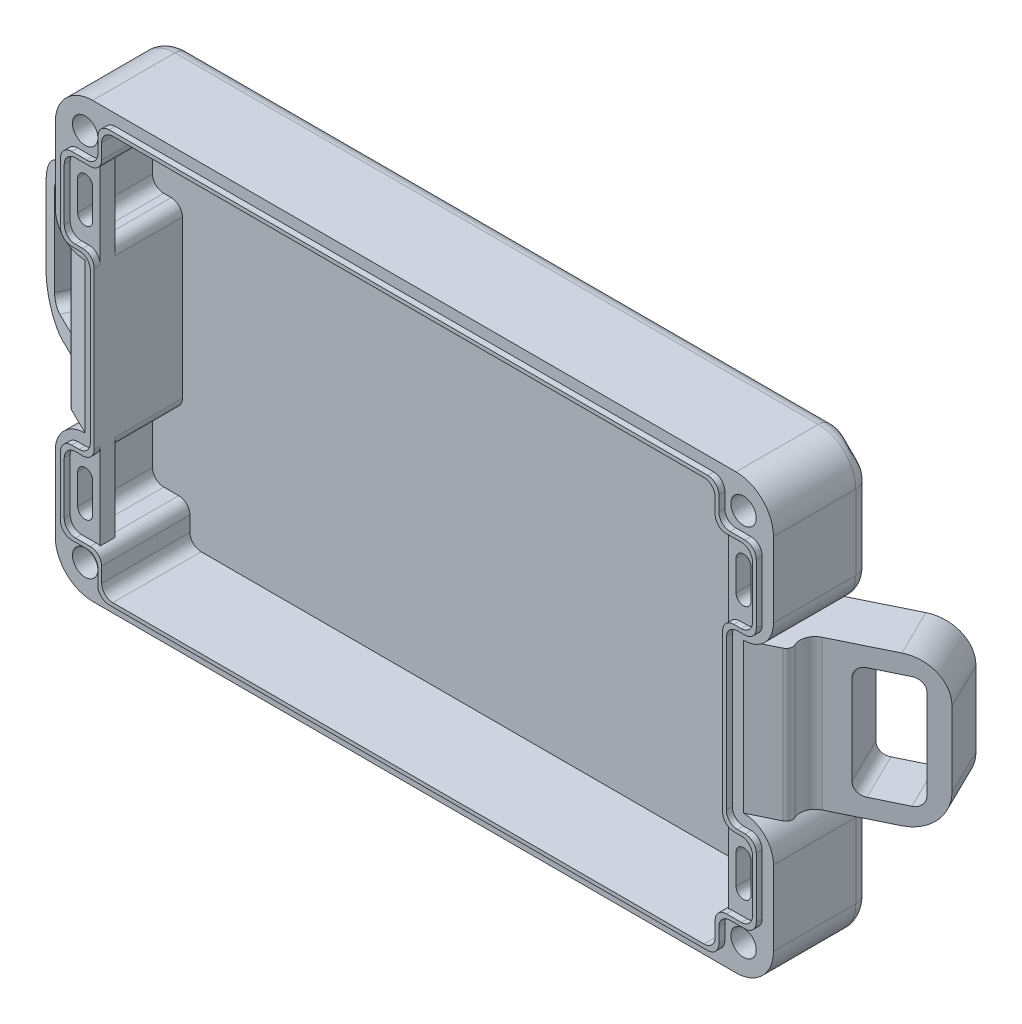
SolidWorks part; units mm, degrees
ref_plane "Спереди" through (0, 0, 0) normal (0, 0, 1) x (1, 0, 0)
ref_plane "Сверху" through (0, 0, 0) normal (0, 1, 0) x (1, 0, 0)
ref_plane "Справа" through (0, 0, 0) normal (1, 0, 0) x (0, 0, -1)
sketch "Sketch1" plane through (0, 0, 0) normal (0, 0, 1) x (1, 0, 0)
  line L1 (-48, 58) -> (48, 58) construction
  line L2 (-48, 58) -> (-48, 0) construction
  line L3 (-48, 0) -> (48, 0) construction
  line L5 (-48, 29) -> (32, 29) construction
  line L7 (0, 0) -> (0, 58) construction
  line L10 (-48, 58) -> (-48, 0) construction
  line L11 (-48, 58) -> (48, 58)
  line L12 (48, 58) -> (48, 0) construction
  line L13 (48, 0) -> (-48, 0)
  line L14 (48, 19) -> (44, 19)
  line L15 (44, 19) -> (44, 39)
  line L16 (44, 39) -> (48, 39)
  line L17 (-44, 39) -> (-48, 39)
  line L18 (-44, 19) -> (-44, 39)
  line L19 (-48, 19) -> (-44, 19)
  line L20 (48, 0) -> (48, 19)
  line L21 (48, 39) -> (48, 58)
  line L22 (-48, 0) -> (-48, 19)
  line L23 (-48, 39) -> (-48, 58)
  dimension "D1" = 96
  dimension "D2" = 58
  dimension "D3" = 4
  dimension "D4" = 10
  dimension "D5" = 10
extrude "Boss-Extrude1" add sketch "Sketch1" along normal blind 13
shell "Shell1" thickness 2 removed face at (0, 29, 13)
sketch "Sketch3" plane through (0, 0, 2) normal (0, 0, 1) x (1, 0, 0)
  line L0 (0, 0) -> (0, 58) construction
  line L1 (46, 2) -> (41, 2)
  line L2 (46, 2) -> (46, 7)
  line L3 (46, 7) -> (41, 7)
  line L4 (41, 2) -> (41, 7)
  line L5 (-48, 0) -> (48, 0) construction
  line L6 (48, 58) -> (-48, 58) construction
  line L7 (-41, 2) -> (-41, 7)
  line L9 (44, 29) -> (-44, 29) construction
  line L11 (-46, 7) -> (-41, 7)
  line L12 (-46, 2) -> (-46, 7)
  line L13 (-46, 2) -> (-41, 2)
  line L14 (-46, 56) -> (-41, 56)
  line L15 (-46, 56) -> (-46, 51)
  line L16 (-46, 51) -> (-41, 51)
  line L17 (-41, 56) -> (-41, 51)
  line L18 (41, 56) -> (41, 51)
  line L19 (46, 51) -> (41, 51)
  line L20 (46, 56) -> (46, 51)
  line L21 (46, 56) -> (41, 56)
  line L22 (48, 0) -> (48, 19) construction
  line L23 (44, 19) -> (44, 39) construction
  line L24 (-44, 39) -> (-44, 19) construction
  circle A0 centre (44, 4) radius 1.7
  circle A1 centre (-44, 4) radius 1.7
  circle A2 centre (-44, 54) radius 1.7
  circle A3 centre (44, 54) radius 1.7
  dimension "D3" = 3.4
  dimension "D1" = 5
  dimension "D2" = 5
  dimension "D4" = 4
  dimension "D5" = 4
extrude "Boss-Extrude3" add sketch "Sketch3" along normal up to surface (11 mm away) up to face at (0, 29, 13)
sketch "Sketch2" plane through (0, 0, 2) normal (0, 0, 1) x (1, 0, 0)
  line L0 (0, 0) -> (0, 58) construction
  line L5 (-48, 0) -> (48, 0) construction
  line L6 (48, 58) -> (-48, 58) construction
  line L7 (44, 19) -> (44, 39) construction
  line L9 (-44, 29) -> (44, 29) construction
  line L11 (-44, 39) -> (-44, 19) construction
  circle A0 centre (-29, 44.5) radius 2.5
  circle A1 centre (29, 44.5) radius 2.5
  circle A2 centre (29, 13.5) radius 2.5
  circle A3 centre (-29, 13.5) radius 2.5
  circle A4 centre (-29, 44.5) radius 1.25
  circle A5 centre (29, 44.5) radius 1.25
  circle A6 centre (29, 13.5) radius 1.25
  circle A7 centre (-29, 13.5) radius 1.25
  dimension "D3" = 5
  dimension "D4" = 29
  dimension "D8" = 31
  dimension "D9" = 2.5
  dimension "D1" = 2
  dimension "D2" = 2
sketch "Sketch5" plane through (0, 0, 13) normal (0, 0, 1) x (1, 0, 0)
  line L0 (0, 0) -> (0, 58) construction
  line L1 (-48, 0) -> (48, 0) construction
  line L2 (48, 58) -> (-48, 58) construction
  line L4 (46, 7) -> (46, 17) construction
  line L5 (44, 29) -> (-42, 29) construction
  line L6 (46, 7) -> (46, 17) construction
  line L8 (46, 7) -> (41, 7)
  line L9 (41, 7) -> (41, 2)
  line L10 (41, 2) -> (0, 2)
  line L11 (-41, 2) -> (41, 2) construction
  line L38 (44, 19) -> (44, 39) construction
  line L39 (-42, 41) -> (-42, 17) construction
  line L40 (42.5, 17.5) -> (42.5, 29)
  line L41 (46.5, 17.5) -> (42.5, 17.5)
  line L42 (46, 7) -> (46, 17)
  line L43 (46, 17) -> (42, 17) construction
  line L44 (46, 17) -> (42, 17) construction
  line L45 (46, 17) -> (42, 17)
  line L46 (42, 17) -> (42, 29)
  line L47 (42, 17) -> (42, 41) construction
  line L48 (46.5, 6.5) -> (46.5, 17.5)
  line L49 (46.5, 6.5) -> (41.5, 6.5)
  line L50 (41.5, 6.5) -> (41.5, 1.5)
  line L51 (41.5, 1.5) -> (0, 1.5)
  line L52 (-41.5, 1.5) -> (0, 1.5)
  line L53 (-41.5, 6.5) -> (-41.5, 1.5)
  line L54 (-46.5, 6.5) -> (-41.5, 6.5)
  line L55 (-46.5, 6.5) -> (-46.5, 17.5)
  line L56 (-42, 17) -> (-42, 41)
  line L57 (-46, 17) -> (-42, 17)
  line L58 (-46, 7) -> (-46, 17)
  line L59 (-46.5, 17.5) -> (-42.5, 17.5)
  line L60 (-42.5, 17.5) -> (-42.5, 40.5)
  line L61 (-41, 2) -> (0, 2)
  line L62 (-41, 7) -> (-41, 2)
  line L63 (-46, 7) -> (-41, 7)
  line L64 (-46, 51) -> (-41, 51)
  line L65 (-41, 51) -> (-41, 56)
  line L66 (-41, 56) -> (0, 56)
  line L67 (-46.5, 40.5) -> (-42.5, 40.5)
  line L68 (-46, 51) -> (-46, 41)
  line L69 (-46, 41) -> (-42, 41)
  line L70 (-46.5, 51.5) -> (-46.5, 40.5)
  line L71 (-46.5, 51.5) -> (-41.5, 51.5)
  line L72 (-41.5, 51.5) -> (-41.5, 56.5)
  line L73 (-41.5, 56.5) -> (0, 56.5)
  line L74 (41.5, 56.5) -> (0, 56.5)
  line L75 (41.5, 51.5) -> (41.5, 56.5)
  line L76 (46.5, 51.5) -> (41.5, 51.5)
  line L77 (46.5, 51.5) -> (46.5, 40.5)
  line L78 (42, 41) -> (42, 29)
  line L79 (46, 41) -> (42, 41)
  line L80 (46, 51) -> (46, 41)
  line L81 (46.5, 40.5) -> (42.5, 40.5)
  line L82 (42.5, 40.5) -> (42.5, 29)
  line L83 (41, 56) -> (0, 56)
  line L84 (41, 51) -> (41, 56)
  line L85 (46, 51) -> (41, 51)
  point P58 (-42.5, 29)
  dimension "D1" = 0.5
extrude "Boss-Extrude4" add sketch "Sketch5" along normal blind 0.8
fillet "Fillet6" radius 1.5 20 edges at (-41, 2, 7.9) (-41, 7, 7.9) (-46, 7, 7.9) (-46, 17, 7.9) (-42, 17, 7.9) (-42, 41, 7.9) (-46, 41, 7.9) (-46, 51, 7.9) (-41, 51, 7.9) (-41, 56, 7.9) (41, 56, 7.9) (41, 51, 7.9) (46, 51, 7.9) (46, 41, 7.9) (42, 41, 7.9) (42, 17, 7.9) (46, 17, 7.9) (41, 2, 7.9) (46, 7, 7.9) (41, 7, 7.9)
fillet "Fillet7" radius 1.5 20 edges at (46.5, 6.5, 13.4) (41.5, 6.5, 13.4) (41.5, 1.5, 13.4) (-41.5, 1.5, 13.4) (-41.5, 6.5, 13.4) (-46.5, 6.5, 13.4) (-46.5, 17.5, 13.4) (-42.5, 17.5, 13.4) (-42.5, 40.5, 13.4) (-46.5, 40.5, 13.4) (-46.5, 51.5, 13.4) (-41.5, 51.5, 13.4) (-41.5, 56.5, 13.4) (41.5, 56.5, 13.4) (41.5, 51.5, 13.4) (46.5, 51.5, 13.4) (46.5, 40.5, 13.4) (42.5, 40.5, 13.4) (42.5, 17.5, 13.4) (46.5, 17.5, 13.4)
sketch "Sketch6" plane through (44, 0, 0) normal (1, 0, 0) x (0, 0, -1)
  line L0 (-13, 19) -> (-13, 39) construction
  line L6 (-13, 19) -> (0, 19) construction
  circle A0 centre (-8, 29) radius 2.5
  dimension "D11" = 5
  dimension "D2" = 10
  dimension "D12" = 5
extrude "Cut-Extrude1" cut sketch "Sketch6" against normal blind 10
fillet "Fillet8" radius 5 4 edges at (-48, 0, 6.5) (-48, 58, 6.5) (48, 58, 6.5) (48, 0, 6.5)
fillet "Fillet9" radius 4 4 edges at (-48, 19, 6.5) (-48, 39, 6.5) (48, 39, 6.5) (48, 19, 6.5)
fillet "Fillet11" radius 2 14 edges at (46.5355, 56.5355, 0) (48, 48, 0) (46.8284, 40.1716, 0) (46.8284, 17.8284, 0) (48, 10, 0) (46.5355, 1.4645, 0) (0, 0, 0) (-46.5355, 1.4645, 0) (-48, 10, 0) (-46.8284, 17.8284, 0) (-46.8284, 40.1716, 0) (-48, 48, 0) (-46.5355, 56.5355, 0) (0, 58, 0)
sketch "Sketch7" plane through (0, 0, 0) normal (0, 0, -1) x (-1, 0, 0)
  line L0 (0, 0) -> (0, 58) construction
  line L1 (10, 8) -> (-10, 8)
  line L2 (10, 8) -> (10, 10)
  line L3 (10, 10) -> (-10, 10)
  line L4 (-10, 8) -> (-10, 10)
  line L5 (-43, 58) -> (43, 58) construction
  line L7 (-44, 19) -> (-44, 39) construction
  line L17 (44, 39) -> (44, 19) construction
  line L18 (39.5, 2) -> (-39.5, 2) construction
  line L19 (44, 29) -> (-44, 29) construction
  line L23 (-10, 50) -> (-10, 48)
  line L24 (10, 48) -> (-10, 48)
  line L25 (10, 50) -> (10, 48)
  line L26 (10, 50) -> (-10, 50)
  dimension "D1" = 20
  dimension "D2" = 10
  dimension "D3" = 2
  dimension "D4" = 6
ref_plane "Plane1" through (0, 29, 0) normal (0, -1, 0) x (-1, 0, 0)
sketch "Sketch10" plane through (0, 29, 0) normal (0, -1, 0) x (-1, 0, 0)
  spline S0 degree 3 poles (-59.8835, 6.9468) (26.7129, -0.1537) (63.2969, 10.7944) (100.6918, 59.242) (162.9949, 234.3824) (61.5213, 355.8312) (-162.0529, 291.2498) (-176.0563, 113.2978) (-59.8835, 6.9468) (26.7129, -0.1537) (63.2969, 10.7944) knots -0.322785 -0.070819 -0.035391 0 0.045461 0.074644 0.13467 0.588936 0.677215 0.929181 0.964609 1 1.045461 1.074644 1.13467 only from (12.8273, 2.9485) to (12.8273, 2.9485)
ref_plane "Plane2" through (0, 0, 0) normal (1, 0, 0) x (0, 0, -1)
ref_plane "Plane3" through (0, 0, 13) normal (0, 0, 1) x (1, 0, 0)
sketch "Sketch14" plane through (0, 0, 13) normal (0, 0, 1) x (1, 0, 0)
  line L0 (44.5, 7) -> (42.5, 7)
  line L5 (46, 8.5) -> (46, 15.5)
  line L7 (44.5, 17) -> (43.5, 17)
  line L8 (42, 18.5) -> (42, 6.9142)
  line L9 (-42, 18.5) -> (-42, 6.9142)
  line L10 (-44.5, 17) -> (-43.5, 17)
  line L12 (-46, 8.5) -> (-46, 15.5)
  line L13 (-44.5, 7) -> (-42.5, 7)
  line L14 (-44.5, 51) -> (-42.5, 51)
  line L15 (-46, 49.5) -> (-46, 42.5)
  line L16 (-44.5, 41) -> (-43.5, 41)
  line L17 (-42, 39.5) -> (-42, 51.0858)
  line L18 (42, 39.5) -> (42, 51.0858)
  line L19 (44.5, 41) -> (43.5, 41)
  line L20 (46, 49.5) -> (46, 42.5)
  line L21 (44.5, 51) -> (42.5, 51)
  arc A0 (44.5, 7) -> (46, 8.5) centre (44.5, 8.5) ccw
  arc A1 (46, 15.5) -> (44.5, 17) centre (44.5, 15.5) ccw
  arc A2 (42.5, 7) -> (42, 6.9142) centre (42.5, 5.5) ccw
  arc A3 (43.5, 17) -> (42, 18.5) centre (43.5, 18.5) cw
  arc A4 (-43.5, 17) -> (-42, 18.5) centre (-43.5, 18.5) ccw
  arc A5 (-42.5, 7) -> (-42, 6.9142) centre (-42.5, 5.5) cw
  arc A6 (-46, 15.5) -> (-44.5, 17) centre (-44.5, 15.5) cw
  arc A7 (-44.5, 7) -> (-46, 8.5) centre (-44.5, 8.5) cw
  arc A8 (-44.5, 51) -> (-46, 49.5) centre (-44.5, 49.5) ccw
  arc A9 (-46, 42.5) -> (-44.5, 41) centre (-44.5, 42.5) ccw
  arc A10 (-42.5, 51) -> (-42, 51.0858) centre (-42.5, 52.5) ccw
  arc A11 (-43.5, 41) -> (-42, 39.5) centre (-43.5, 39.5) cw
  arc A12 (43.5, 41) -> (42, 39.5) centre (43.5, 39.5) ccw
  arc A13 (42.5, 51) -> (42, 51.0858) centre (42.5, 52.5) cw
  arc A14 (46, 42.5) -> (44.5, 41) centre (44.5, 42.5) cw
  arc A15 (44.5, 51) -> (46, 49.5) centre (44.5, 49.5) cw
  point P20 (0, 0)
  point P66 (0, 58)
extrude "Boss-Extrude8" add sketch "Sketch14" against normal blind 2
sketch "Sketch15" plane through (0, 0, 13) normal (0, 0, 1) x (1, 0, 0)
  line L0 (44, 10) -> (44, 14) construction
  line L1 (43, 10) -> (43, 14)
  line L2 (45, 10) -> (45, 14)
  line L4 (42.5, 7) -> (44.5, 7) construction
  line L6 (42, 18.5) -> (42, 6.9142) construction
  line L8 (0, 0) -> (0, 58) construction
  line L9 (-43, 0) -> (43, 0) construction
  line L10 (-44, 10) -> (-44, 14) construction
  line L11 (44, 19) -> (44, 39) construction
  line L12 (44, 29) -> (-44, 29) construction
  line L13 (-43, 10) -> (-43, 14)
  line L14 (-45, 10) -> (-45, 14)
  line L15 (44, 48) -> (44, 44) construction
  line L16 (43, 48) -> (43, 44)
  line L17 (45, 48) -> (45, 44)
  line L18 (-44, 48) -> (-44, 44) construction
  line L19 (-43, 48) -> (-43, 44)
  line L20 (-45, 48) -> (-45, 44)
  arc A0 (43, 10) -> (45, 10) centre (44, 10) ccw
  arc A1 (45, 14) -> (43, 14) centre (44, 14) ccw
  arc A2 (-43, 10) -> (-45, 10) centre (-44, 10) cw
  arc A3 (-45, 14) -> (-43, 14) centre (-44, 14) cw
  arc A4 (43, 48) -> (45, 48) centre (44, 48) cw
  arc A5 (45, 44) -> (43, 44) centre (44, 44) cw
  arc A6 (-43, 48) -> (-45, 48) centre (-44, 48) ccw
  arc A7 (-45, 44) -> (-43, 44) centre (-44, 44) ccw
  point P2 (44, 12)
  point P7 (44, 15)
  point P12 (44, 9)
  point P25 (-44, 12)
  point P30 (-44, 9)
  point P31 (-44, 15)
  point P34 (44, 46)
  point P41 (-44, 46)
  point P46 (-44, 43)
  point P47 (-44, 49)
  point P48 (44, 49)
  point P49 (44, 43)
  dimension "D1" = 2
  dimension "D2" = 6
  dimension "D3" = 2
  dimension "D4" = 1
extrude "Cut-Extrude4" cut sketch "Sketch15" against normal blind 2
sketch "Sketch17" plane through (0, 0, 0) normal (0, 0, -1) x (-1, 0, 0)
  line L0 (0, 0) -> (0, 58) construction
  line L2 (-43, 58) -> (43, 58) construction
  line L3 (0, 58) -> (44, 29) construction
  line L4 (44, 29) -> (-44, 29) construction
  line L5 (43, 0) -> (-43, 0) construction
  circle A0 centre (44, 4) radius 1.7
  circle A1 centre (-44, 4) radius 1.7
  circle A2 centre (-44, 54) radius 1.7
  circle A3 centre (44, 54) radius 1.7
  dimension "D1" = 3.4
extrude "Cut-Extrude5" cut sketch "Sketch17" against normal blind 10
sketch "Sketch18" plane through (0, 0, 0) normal (0, 0, -1) x (-1, 0, 0)
  line L0 (0, 0) -> (0, 58) construction
  line L2 (-43, 58) -> (43, 58) construction
  line L3 (-44, 19) -> (-44, 39) construction
  line L5 (44, 29) -> (-44, 29) construction
  line L7 (44, 39) -> (44, 19) construction
  circle A0 centre (44, 4) radius 2.5
  circle A1 centre (-44, 4) radius 2.5
  circle A2 centre (-44, 54) radius 2.5
  circle A3 centre (44, 54) radius 2.5
  dimension "D1" = 5
extrude "Cut-Extrude6" cut sketch "Sketch18" against normal blind 5
fillet "Fillet16" radius 0.5 16 edges at (-45.4832, 56.0125, 0.216) (-46.0125, 2.5168, 0.216) (-42.2322, 5.7678, 0) (45.4832, 1.9875, 0.216) (42.2322, 52.2322, 0) (-42.2322, 52.2322, 0) (42.2322, 5.7678, 0) (46.0125, 55.4832, 0.216)
ref_plane "Plane4" through (0, 19, 0) normal (0, -1, 0) x (-1, 0, 0)
sketch "Sketch19" plane through (0, 19, 0) normal (0, -1, 0) x (1, 0, 0)
  line L0 (44, 2) -> (47.9572, 10.0793)
  line L1 (47.553, 11.2598) -> (44, 13)
  line L2 (44, 2) -> (44, 13)
  line L5 (0, 0) -> (0, 32.8413) construction
  line L6 (-44, 2) -> (-44, 13)
  line L7 (-47.553, 11.2598) -> (-44, 13)
  line L8 (-44, 2) -> (-47.9572, 10.0793)
  line L14 (44, 5.5) -> (44, 10.5) construction
  line L15 (43, 13) -> (45, 13) construction
  arc A0 (47.9572, 10.0793) -> (47.553, 11.2598) centre (47.1649, 10.4674) ccw
  arc A2 (-47.9572, 10.0793) -> (-47.553, 11.2598) centre (-47.1649, 10.4674) cw
  dimension "D1" = 11
extrude "Boss-Extrude9" add sketch "Sketch19" against normal blind 20
sketch "Sketch20" plane through (34.6967, 0, -16.9943) normal (0.8981, 0, -0.4399) x (-0.4399, 0, -0.8981)
  line L0 (-28.1467, 19) -> (-28.1467, 39)
  line L1 (-21.1503, 19) -> (-28.1467, 19)
  line L2 (-21.1503, 19) -> (-21.1503, 39)
  line L3 (-21.1503, 39) -> (-28.1467, 39)
  line L5 (-30.1467, 39) -> (-30.1467, 19) construction
  line L6 (-21.1503, 39) -> (-30.1467, 39) construction
  dimension "D1" = 2
extrude "Boss-Extrude10" add sketch "Sketch20" along normal blind 15
ref_plane "Plane5" through (0, 0, 0) normal (1, 0, 0) x (0, 0, -1)
sketch "Sketch21" plane through (12.3808, 0, 25.2775) normal (0.4399, 0, 0.8981) x (0.8981, 0, -0.4399)
  line L0 (51.135, 36.5) -> (51.135, 21.5)
  line L5 (53.635, 39) -> (38.635, 39) construction
  line L6 (53.635, 39) -> (53.635, 19) construction
  line L7 (53.635, 19) -> (38.635, 19) construction
  line L8 (38.635, 39) -> (38.635, 19) construction
  line L9 (51.135, 21.5) -> (43.635, 21.5)
  line L11 (51.135, 36.5) -> (43.635, 36.5)
  line L12 (43.635, 21.5) -> (43.635, 36.5)
  line L13 (51.135, 21.5) -> (41.135, 21.5) construction
  line L14 (41.135, 36.5) -> (41.135, 21.5) construction
  line L15 (51.135, 36.5) -> (41.135, 36.5) construction
  dimension "D1" = 5
extrude "Cut-Extrude7" cut sketch "Sketch21" against normal blind 10
mirror "Mirror1" about plane through (0, 0, 0) normal (1, 0, 0) of "Boss-Extrude10", "Cut-Extrude7"
fillet "Fillet17" radius 5 4 edges at (-59.0097, 39, -1.4564) (-59.0097, 19, -1.4564) (59.0097, 39, -1.4564) (59.0097, 19, -1.4564)
fillet "Fillet18" radius 1.5 6 edges at (-56.7645, 36.5, -0.3567) (-56.7645, 21.5, -0.3567) (56.7645, 36.5, -0.3567) (56.7645, 21.5, -0.3567) (50.0291, 36.5, 2.9423) (50.0291, 21.5, 2.9423)
fillet "Fillet19" radius 2 2 edges at (-47.0775, 29, 8.2832) (47.0775, 29, 8.2832)
